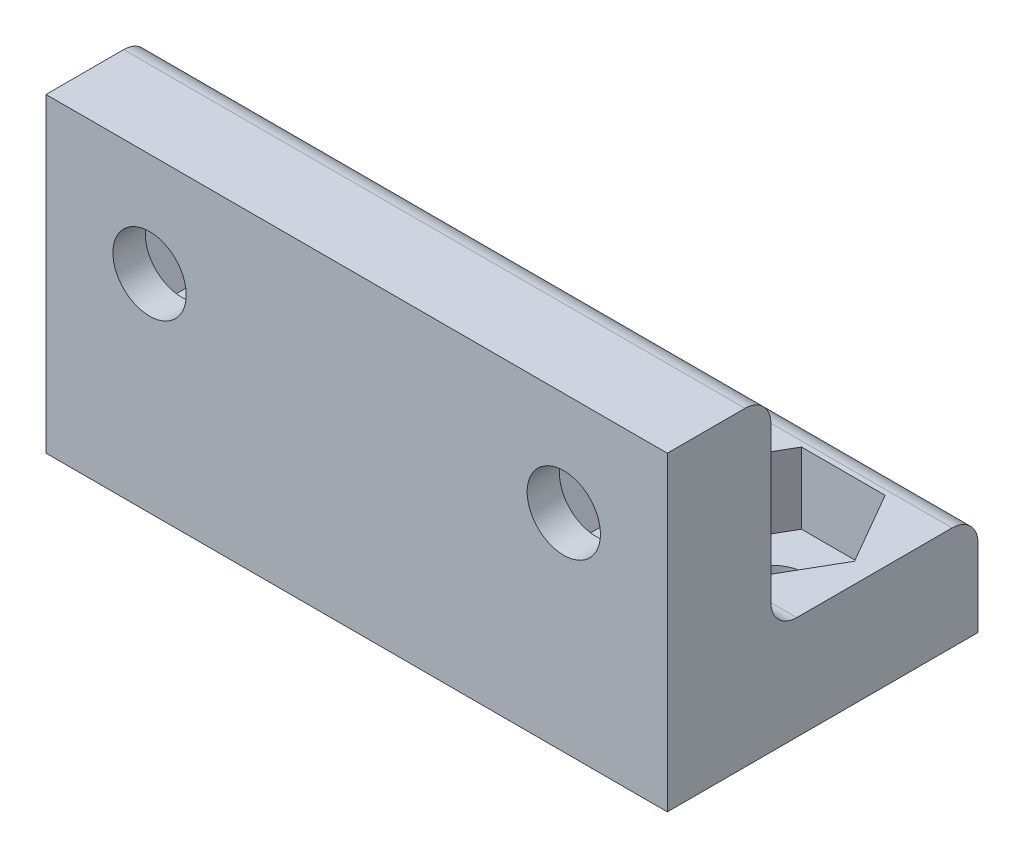
SolidWorks part; units mm, degrees
material "PET"
ref_plane "Front Plane" through (0, 0, 0) normal (0, 0, 1) x (1, 0, 0)
ref_plane "Top Plane" through (0, 0, 0) normal (0, 1, 0) x (1, 0, 0)
ref_plane "Right Plane" through (0, 0, 0) normal (1, 0, 0) x (0, 0, -1)
sketch "Sketch1" plane through (0, 0, 0) normal (1, 0, 0) x (0, 0, -1)
  line L0 (0, 0) -> (6.35, 6.35)
  line L1 (6.35, 6.35) -> (19.05, 6.35)
  line L2 (19.05, 6.35) -> (19.05, 0)
  line L3 (19.05, 0) -> (0, 0)
  dimension "D1" = 45
  dimension "D2" = 6.35
  dimension "D3" = 19.05
extrude "Boss-Extrude1" add sketch "Sketch1" along normal mid plane 38.1
sketch "Sketch2" plane through (0, 6.35, 0) normal (0, 1, 0) x (1, 0, 0)
  line L0 (19.05, 19.05) -> (-19.05, 19.05) construction
  line L1 (-17.829, 12.7) -> (-15.2645, 8.2582)
  line L2 (-15.2645, 8.2582) -> (-10.1355, 8.2582)
  line L3 (-10.1355, 8.2582) -> (-7.571, 12.7)
  line L4 (-7.571, 12.7) -> (-10.1355, 17.1418)
  line L5 (-10.1355, 17.1418) -> (-15.2645, 17.1418)
  line L6 (-15.2645, 17.1418) -> (-17.829, 12.7)
  line L7 (-19.05, 19.05) -> (-19.05, 6.35) construction
  line L8 (0, 6.35) -> (0, 19.05) construction
  line L9 (19.05, 6.35) -> (-19.05, 6.35) construction
  line L10 (15.2645, 17.1418) -> (17.829, 12.7)
  line L11 (10.1355, 17.1418) -> (15.2645, 17.1418)
  line L12 (7.571, 12.7) -> (10.1355, 17.1418)
  line L13 (10.1355, 8.2582) -> (7.571, 12.7)
  line L14 (15.2645, 8.2582) -> (10.1355, 8.2582)
  line L15 (17.829, 12.7) -> (15.2645, 8.2582)
  circle A0 centre (-12.7, 12.7) radius 4.4418 construction
  circle A1 centre (12.7, 12.7) radius 4.4418 construction
  circle A2 centre (-12.7, 12.7) radius 2.2479
  circle A3 centre (12.7, 12.7) radius 2.2479
  dimension "D1" = 8.8836
  dimension "D4" = 4.4958
  dimension "D2" = 6.35
  dimension "D3" = 6.35
extrude "Cut-Extrude1" cut sketch "Sketch2" against normal blind 4.3656
extrude "Cut-Extrude2" cut sketch "Sketch2<2>" against normal through all contours A2 | A3 region at (-12.7, 6.35, -12.7) region at (12.7, 6.35, -12.7)
sketch "Sketch2<2>" plane through (0, 6.35, 0) normal (0, 1, 0) x (1, 0, 0) same geometry as "Sketch2"
mirror "Mirror1" about plane through (19.05, 0, 0) normal (0, -0.7071, -0.7071) of bodies 103
fillet "Fillet1" radius 1.5875 1 edges at (0, 6.35, -6.35)
fillet "Fillet2" radius 1.5875 2 edges at (0, 6.35, -19.05) (0, 19.05, -6.35)
